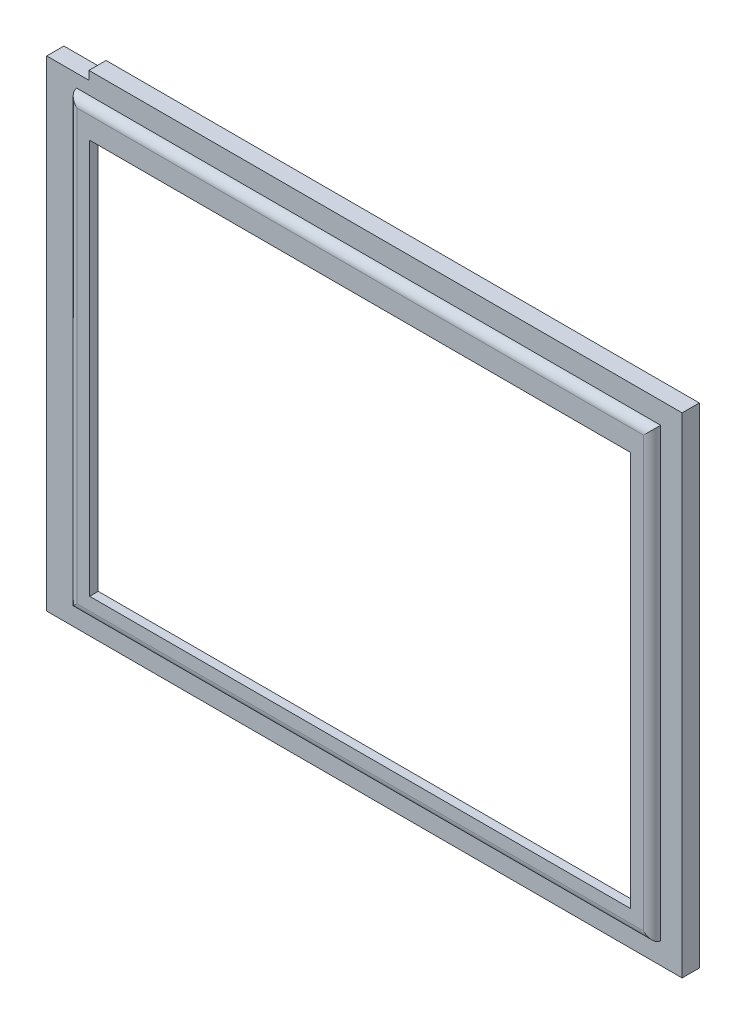
SolidWorks part; units mm, degrees
material "Borracha"
ref_plane "Plano frontal" through (0, 0, 0) normal (0, 0, 1) x (1, 0, 0)
ref_plane "Plano superior" through (0, 0, 0) normal (0, 1, 0) x (1, 0, 0)
ref_plane "Plano direito" through (0, 0, 0) normal (1, 0, 0) x (0, 0, -1)
other "plano sup"
sketch "Esboço2" plane through (0, 0, 0) normal (0, 0, 1) x (1, 0, 0)
  line L0 (0, 0) -> (740, 0)
  line L12 (0, 0) -> (0, -570)
  line L13 (0, -570) -> (740, -570)
  line L14 (740, -570) -> (740, 0)
  line L23 (35, -25) -> (715, -25)
  line L24 (35, -25) -> (35, -545)
  line L25 (35, -545) -> (715, -545)
  line L26 (715, -25) -> (715, -545)
  dimension "D3" = 35
  dimension "D1" = 740
  dimension "D2" = 570
  dimension "D4" = 25
  dimension "D5" = 25
  dimension "D6" = 25
extrude "Ressalto-extrusão1" add sketch "Esboço2" along normal blind 20
ref_plane "Plano1" through (0, 0, 20) normal (0, 0, 1) x (1, 0, 0)
sketch "Esboço3" plane through (0, 0, 20) normal (0, 0, 1) x (1, 0, 0)
  line L1 (35, -25) -> (715, -25)
  line L2 (35, -25) -> (35, -545)
  line L3 (35, -545) -> (715, -545)
  line L4 (715, -25) -> (715, -545)
  line L5 (60, -520) -> (690, -520)
  line L6 (60, -520) -> (60, -60)
  line L7 (60, -60) -> (690, -60)
  line L8 (690, -520) -> (690, -60)
  dimension "D1" = 35
  dimension "D2" = 25
  dimension "D3" = 25
  dimension "D4" = 25
extrude "Ressalto-extrusão2" add sketch "Esboço3" along normal blind 10 separate body
fillet "Filete1" radius 10 4 edges at (35, -285, 30) (375, -545, 30) (715, -285, 30) (375, -25, 30) type face fillet first side face at (375, -285, 30) second side face at (375, -545, 25) second side face at (35, -285, 25) second side face at (375, -25, 25) second side face at (715, -285, 25)
sketch "Esboço4" plane through (0, 0, 20) normal (0, 0, 1) x (1, 0, 0)
  line L1 (0, 0) -> (49.1432, 0)
  line L2 (0, 0) -> (0, -10)
  line L3 (0, -10) -> (49.1432, -10)
  line L4 (49.1432, 0) -> (49.1432, -10)
  dimension "D1" = 49.1432
  dimension "D2" = 10
extrude "Corte-extrusão1" cut sketch "Esboço4" against normal up to next (20 mm away)
